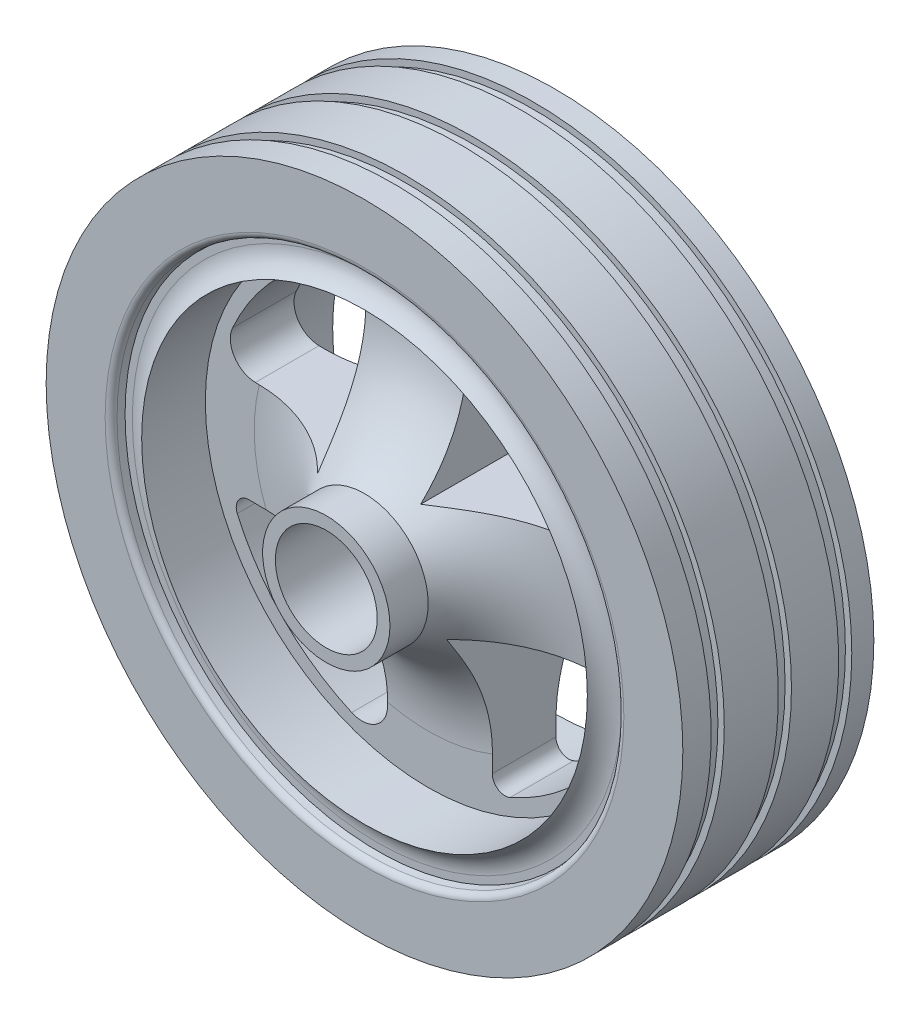
SolidWorks part; units mm, degrees
ref_plane "Front Plane" through (0, 0, 0) normal (0, 0, 1) x (1, 0, 0)
ref_plane "Top Plane" through (0, 0, 0) normal (0, 1, 0) x (1, 0, 0)
ref_plane "Right Plane" through (0, 0, 0) normal (1, 0, 0) x (0, 0, -1)
sketch "Sketch1" plane through (0, 0, 0) normal (0, 0, 1) x (1, 0, 0)
  circle A0 centre (0, 0) radius 25
  dimension "D1" = 50
extrude "Boss-Extrude1" add sketch "Sketch1" along normal mid plane 15
sketch "Sketch2" plane through (0, 0, 7.5) normal (0, 0, 1) x (1, 0, 0)
  circle A0 centre (0, 0) radius 17.5
  circle A1 centre (0, 0) radius 5
  dimension "D1" = 35
  dimension "D2" = 10
extrude "Cut-Extrude1" cut sketch "Sketch2" against normal blind 5 contours A0 A1 | A1
mirror "Mirror2" about plane through (0, 0, 0) normal (0, 0, 1) of "Cut-Extrude1"
fillet "Fillet1" radius 10 1 edges at (5, 0, 2.5)
fillet "Fillet2" radius 10 1 edges at (5, 0, -2.5)
sketch "Sketch5" plane through (0, 0, 2.5) normal (0, 0, 1) x (1, 0, 0)
  line L0 (5.0954, -3.0719) -> (5.0344, -14.0339)
  line L3 (3.0435, 5.1125) -> (14.0057, 5.1125)
  line L4 (3.0435, 5.1125) -> (3.0435, 13.6225)
  line L5 (5.0954, -3.0719) -> (13.6054, -3.1193)
  line L6 (-3.1002, -5.0783) -> (-14.0617, -4.9563)
  line L7 (-3.1002, -5.0783) -> (-3.1949, -13.5878)
  line L8 (-5.0609, 3.1284) -> (-4.8779, 14.089)
  line L9 (-5.0609, 3.1284) -> (-13.5698, 3.2705)
  circle A1 centre (0, 0) radius 17.5 construction
  arc A3 (5.8304, 15.4612) -> (14.9184, 6.5209) centre (-1.0551, -0.6273) cw
  arc A4 (5.8304, 15.4612) -> (3.0435, 13.6225) centre (5.0435, 13.6225) ccw
  arc A5 (14.0057, 5.1125) -> (14.9184, 6.5209) centre (14.0057, 6.1125) ccw
  arc A6 (5.0344, -14.0339) -> (6.4378, -14.9545) centre (6.0344, -14.0395) ccw
  arc A7 (15.4285, -5.9164) -> (6.4378, -14.9545) centre (-0.6214, 1.0586) cw
  arc A8 (15.4285, -5.9164) -> (13.6054, -3.1193) centre (13.5943, -5.1192) ccw
  arc A9 (-14.0617, -4.9563) -> (-14.9901, -6.3545) centre (-14.0728, -5.9562) ccw
  arc A10 (-6.0021, -15.3954) -> (-14.9901, -6.3545) centre (1.062, 0.6155) cw
  arc A11 (-6.0021, -15.3954) -> (-3.1949, -13.5878) centre (-5.1948, -13.5656) ccw
  arc A12 (-4.8779, 14.089) -> (-6.271, 15.0252) centre (-5.8778, 14.1057) ccw
  arc A13 (-15.3617, 6.0877) -> (-6.271, 15.0252) centre (0.6096, -1.0654) cw
  arc A14 (-15.3617, 6.0877) -> (-13.5698, 3.2705) centre (-13.5365, 5.2702) ccw
  point P5 (3.0435, 16.386)
  point P11 (15.4769, 5.1125)
  point P40 (0, 0)
  dimension "D3" = 4.0986
  dimension "D6" = 17.5
  dimension "D8" = 2
  dimension "D9" = 1
  dimension "D1" = 11.2735
  dimension "D2" = 5.1125
  dimension "D4" = 12.4334
  dimension "D5" = 90
  dimension "D7" = 16.6663
  dimension "D10" = 4
extrude "Cut-Extrude2" cut sketch "Sketch5" against normal through all
sketch "Sketch6" plane through (0, 0, -2.5) normal (0, 0, -1) x (-1, 0, 0)
  line L0 (5.0609, 3.1284) -> (4.9003, 12.7511) construction
  line L1 (5.0609, 3.1284) -> (4.9003, 12.7511)
  line L4 (13.2642, 3.2654) -> (5.0609, 3.1284)
  arc A1 (13.2642, 3.2654) -> (4.9003, 12.7511) centre (0, 0) ccw
extrude "Cut-Extrude3" cut sketch "Sketch6" against normal through all
ref_plane "Plane1" through (12.6675, 5.1125, 2.5) normal (1, 0, 0) x (0, 0, -1)
sketch "Sketch8" plane through (0, 0, 2.5) normal (0, 0, -1) x (-1, 0, 0)
  line L2 (-12.6675, 5.1125) -> (-3.0435, 5.1125)
  line L3 (-3.0435, 5.1125) -> (-3.0435, 13.3169)
  line L4 (-12.6675, 5.1125) -> (-3.0435, 5.1125)
  line L5 (-3.0435, 5.1125) -> (-3.0435, 13.3169)
  arc A1 (-3.0435, 13.3169) -> (-12.6675, 5.1125) centre (0, 0) ccw
  arc A2 (-3.0435, 13.3169) -> (-12.6675, 5.1125) centre (0, 0) ccw
  dimension "D1" = 0
extrude "Cut-Extrude4" cut sketch "Sketch8" against normal through all
sketch "Sketch9" plane through (0, 0, 2.5) normal (0, 0, -1) x (-1, 0, 0)
  line L2 (-5.0419, -12.6957) -> (-5.0954, -3.0719)
  line L3 (-5.0954, -3.0719) -> (-13.2998, -3.1176)
  line L4 (-5.0419, -12.6957) -> (-5.0954, -3.0719)
  line L5 (-5.0954, -3.0719) -> (-13.2998, -3.1176)
  arc A1 (-13.2998, -3.1176) -> (-5.0419, -12.6957) centre (0, 0) ccw
  arc A2 (-13.2998, -3.1176) -> (-5.0419, -12.6957) centre (0, 0) ccw
  dimension "D1" = 0
extrude "Cut-Extrude5" cut sketch "Sketch9" against normal through all
sketch "Sketch10" plane through (0, 0, 2.5) normal (0, 0, -1) x (-1, 0, 0)
  line L2 (12.7236, -4.9712) -> (3.1002, -5.0783)
  line L3 (3.1002, -5.0783) -> (3.1915, -13.2822)
  line L4 (12.7236, -4.9712) -> (3.1002, -5.0783)
  line L5 (3.1002, -5.0783) -> (3.1915, -13.2822)
  arc A1 (3.1915, -13.2822) -> (12.7236, -4.9712) centre (0, 0) ccw
  arc A2 (3.1915, -13.2822) -> (12.7236, -4.9712) centre (0, 0) ccw
  dimension "D1" = 0
extrude "Cut-Extrude6" cut sketch "Sketch10" against normal through all
sketch "Sketch11" plane through (0, 0, 7.5) normal (0, 0, 1) x (1, 0, 0)
  circle A1 centre (0, 0) radius 5
  circle A2 centre (0, 0) radius 5
  dimension "D1" = 0
extrude "Boss-Extrude2" add sketch "Sketch11" along normal blind 3
sketch "Sketch13" plane through (0, 0, 10.5) normal (0, 0, 1) x (1, 0, 0)
  circle A0 centre (0, 0) radius 4
  circle A1 centre (0, 0) radius 5
  circle A2 centre (0, 0) radius 5
  dimension "D1" = 0
  dimension "D2" = 1
extrude "Cut-Extrude7" cut sketch "Sketch13" against normal blind 13 contours A0
fillet "Fillet3" radius 5 1 edges at (5, 0, -7.5)
sketch "Sketch14" plane through (0, 0, -7.5) normal (0, 0, -1) x (-1, 0, 0)
  circle A0 centre (0, 0) radius 19.9262
  circle A1 centre (0, 0) radius 17.5
  dimension "D1" = 39.8524
  dimension "D2" = 35
extrude "Cut-Extrude8" cut sketch "Sketch14" against normal blind 1 draft 7
fillet "Fillet4" radius 2 1 edges at (-17.6228, 0, -6.5)
fillet "Fillet5" radius 0.5 1 edges at (-19.9262, 0, -7.5)
mirror "Mirror5" about plane through (0, 0, 0) normal (0, 0, 1) of "Fillet4", "Cut-Extrude8"
fillet "Fillet6" radius 0.5 1 edges at (-19.9262, 0, 7.5)
sketch "Sketch15" plane through (0, 0, 0) normal (0, 1, 0) x (1, 0, 0)
  line L0 (25, 7.5) -> (-25, 7.5) construction
  line L1 (26.3205, 5.7669) -> (24.5, 5.7669)
  line L2 (26.3205, 5.7669) -> (26.3205, 4.7379)
  line L3 (26.3205, 4.7379) -> (24.5, 4.7379)
  line L4 (24.5, 5.7669) -> (24.5, 4.7379)
  line L5 (24.5, 0) -> (26.3205, 0)
  line L6 (24.5, 0) -> (24.5, 1.029)
  line L7 (24.5, 1.029) -> (26.3205, 1.029)
  line L8 (26.3205, 0) -> (26.3205, 1.029)
  line L9 (24.5, -5.275) -> (26.3205, -5.275)
  line L10 (24.5, -5.275) -> (24.5, -4.246)
  line L11 (24.5, -4.246) -> (26.3205, -4.246)
  line L12 (26.3205, -5.275) -> (26.3205, -4.246)
  line L13 (-25, -7.5) -> (25, -7.5) construction
  line L14 (0, 16.5257) -> (0, -17.9439) construction
  line L15 (25, -7.5) -> (25, 7.5) construction
  dimension "D1" = 1.029
  dimension "D2" = 1.7331
  dimension "D3" = 2.225
  dimension "D4" = 4.246
  dimension "D5" = 1.8205
  dimension "D6" = 8.9839
  dimension "D7" = 0.5
  dimension "D8" = 1.3205
  dimension "D9" = 1.8205
  dimension "D10" = 1.3205
revolve "Cut-Revolve1" cut sketch "Sketch15" angle 360 about L14
